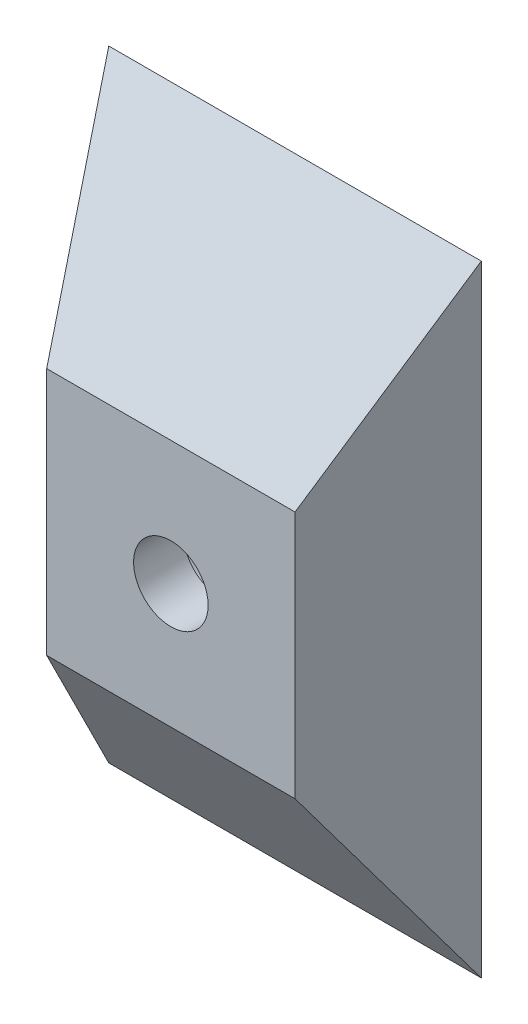
SolidWorks part; units mm, degrees
ref_plane "Alzado" through (0, 0, 0) normal (0, 0, 1) x (1, 0, 0)
ref_plane "Planta" through (0, 0, 0) normal (0, 1, 0) x (1, 0, 0)
ref_plane "Vista lateral" through (0, 0, 0) normal (1, 0, 0) x (0, 0, -1)
sketch "Croquis1" plane through (0, 0, 0) normal (0, 0, 1) x (1, 0, 0)
  line L1 (-7.5, -12.5) -> (7.5, -12.5)
  line L2 (-7.5, -12.5) -> (-7.5, 12.5)
  line L3 (-7.5, 12.5) -> (7.5, 12.5)
  line L4 (7.5, -12.5) -> (7.5, 12.5)
  line L5 (-7.5, -12.5) -> (7.5, 12.5) construction
  line L6 (-7.5, 12.5) -> (7.5, -12.5) construction
  point P0 (0, 0)
  dimension "D1" = 15
  dimension "D2" = 25
ref_plane "Plano1" through (0, 0, 5) normal (0, 0, 1) x (1, 0, 0)
sketch "Croquis9" plane through (0, 0, 5) normal (0, 0, 1) x (1, 0, 0)
  line L1 (-5, 5) -> (5, 5)
  line L2 (-5, 5) -> (-5, -5)
  line L3 (-5, -5) -> (5, -5)
  line L4 (5, 5) -> (5, -5)
  line L5 (-5, 5) -> (5, -5) construction
  line L6 (-5, -5) -> (5, 5) construction
  point P0 (0, 0)
  dimension "D1" = 10
loft "Recubrir1" add profiles "Croquis1", "Croquis9" connector at (7.5, -12.5, 0) connector at (5, -5, 5)
sketch "Croquis10" plane through (0, 0, 5) normal (0, 0, 1) x (1, 0, 0)
  circle A0 centre (0, 0) radius 1.5
  dimension "D1" = 3
extrude "Cortar-Extruir1" cut sketch "Croquis10" against normal blind 5
sketch "Croquis11" plane through (0, 0, 0) normal (0, 0, -1) x (-1, 0, 0)
  circle A0 centre (0, 0) radius 2.5
  dimension "D1" = 5
extrude "Cortar-Extruir2" cut sketch "Croquis11" against normal blind 3
